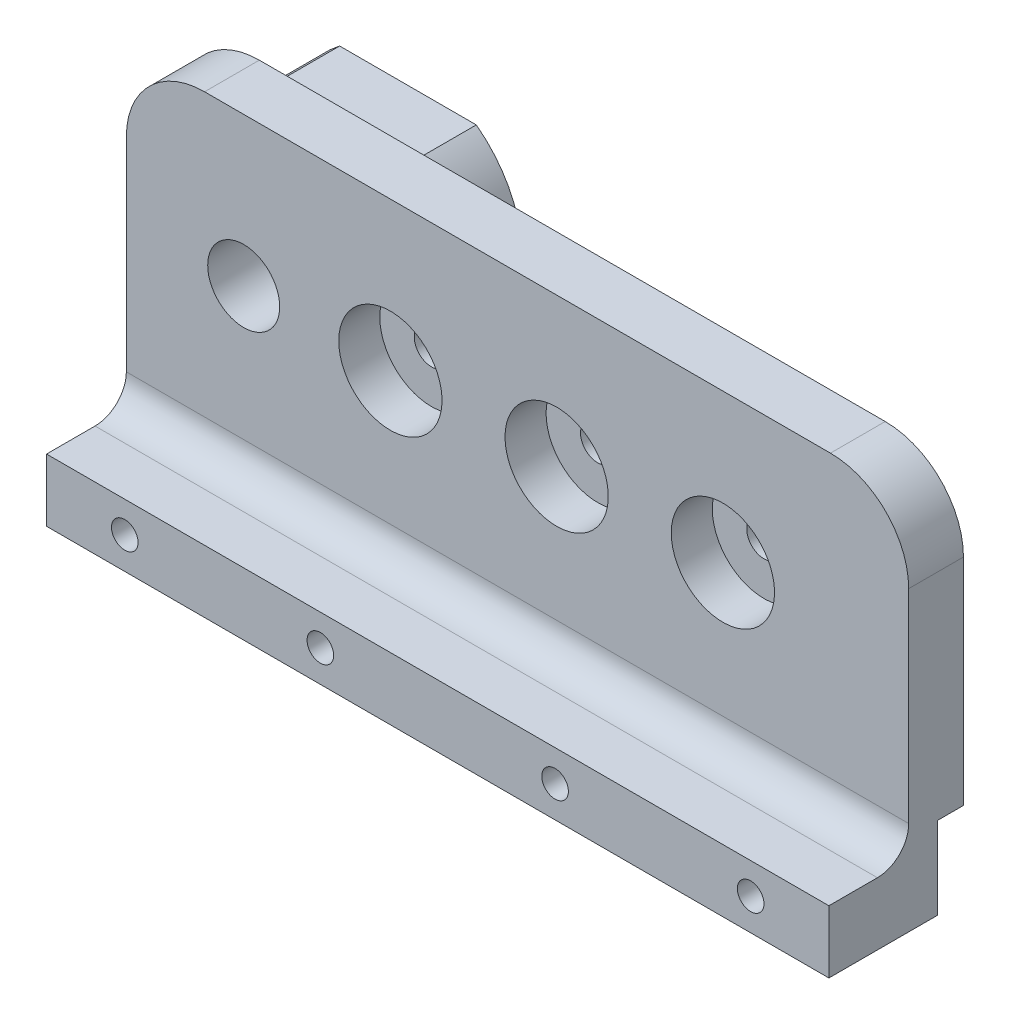
SolidWorks part; units mm, degrees
ref_plane "Front Plane" through (0, 0, 0) normal (0, 0, 1) x (1, 0, 0)
ref_plane "Top Plane" through (0, 0, 0) normal (0, 1, 0) x (1, 0, 0)
ref_plane "Right Plane" through (0, 0, 0) normal (1, 0, 0) x (0, 0, -1)
sketch "Sketch1" plane through (0, 0, 0) normal (0, 0, 1) x (1, 0, 0)
  line L1 (0, 0) -> (100, 0)
  line L2 (0, 0) -> (0, 48)
  line L3 (0, 48) -> (100, 48)
  line L4 (100, 0) -> (100, 48)
  dimension "D1" = 100
  dimension "D2" = 48
extrude "Boss-Extrude1" add sketch "Sketch1" along normal blind 7
sketch "Sketch2" plane through (0, 0, 7) normal (0, 0, 1) x (1, 0, 0)
  line L0 (0, 0) -> (100, 0) construction
  line L1 (0, 48) -> (0, 0) construction
  circle A0 centre (15, 29) radius 4.6
  circle A1 centre (33.75, 29) radius 2.2
  circle A2 centre (55, 29) radius 2.2
  circle A3 centre (76.25, 29) radius 2.2
  dimension "D1" = 4.4
  dimension "D2" = 18.75
  dimension "D3" = 21.25
  dimension "D4" = 21.25
  dimension "D5" = 29
  dimension "D6" = 15
  dimension "D7" = 9.2
extrude "Cut-Extrude1" cut sketch "Sketch2" against normal up to next
sketch "Sketch3" plane through (0, 0, 0) normal (0, 0, -1) x (-1, 0, 0)
  line L0 (0, 48) -> (0, 0) construction
  line L1 (-100, 0) -> (0, 0)
  line L2 (-100, 0) -> (-100, 8)
  line L3 (-100, 8) -> (0, 8)
  line L4 (0, 0) -> (0, 8)
  dimension "D1" = 8
extrude "Boss-Extrude2" add sketch "Sketch3" along normal blind 10.2
sketch "Sketch4" plane through (0, 0, 0) normal (0, 0, -1) x (-1, 0, 0)
  circle A0 centre (-76.25, 29) radius 6.6
  circle A1 centre (-55, 29) radius 6.6
  circle A2 centre (-33.75, 29) radius 6.6
  dimension "D1" = 13.2
extrude "Cut-Extrude2" cut sketch "Sketch4" against normal blind 5.25
sketch "Sketch5" plane through (0, 0, 7) normal (0, 0, 1) x (1, 0, 0)
  line L0 (35, 4.0521) -> (65, 4) construction
  line L1 (0, 0) -> (100, 0) construction
  circle A0 centre (35, 4.0521) radius 2.6
  circle A1 centre (65, 4) radius 2.6
  point P6 (50, 0)
  point P7 (50, 4.0261)
  dimension "D1" = 5.2
  dimension "D2" = 30
  dimension "D3" = 4
extrude "Cut-Extrude3" cut sketch "Sketch5" against normal blind 0.1
sketch "Sketch7" plane through (0, 0, 6.9) normal (0, 0, 1) x (1, 0, 0)
  circle A0 centre (35, 4.0521) radius 1.7
  circle A1 centre (65, 4) radius 1.7
  dimension "D1" = 3.4
extrude "Cut-Extrude4" cut sketch "Sketch7" against normal through all
sketch "Sketch8" plane through (0, 0, 7) normal (0, 0, 1) x (1, 0, 0)
  line L0 (10, 4.0521) -> (35, 4.0521) construction
  line L1 (0, 48) -> (0, 0) construction
  line L2 (100, 0) -> (100, 48) construction
  circle A0 centre (10, 4.0521) radius 1.7
  circle A1 centre (90, 4.0521) radius 1.7
  dimension "D1" = 3.4
  dimension "D2" = 10
  dimension "D3" = 10
extrude "Cut-Extrude5" cut sketch "Sketch8" against normal up to next
mirror "Mirror1" about plane through (0, 0, -10.2) normal (0, 0, 1) of bodies 110
delete or keep bodies "Body-Delete/Keep 1" type delete bodies bodies 110
sketch "Sketch9" plane through (100, 0, 0) normal (1, 0, 0) x (0, 0, -1)
  line L1 (27.4, 0) -> (24.1, 0)
  line L2 (27.4, 0) -> (27.4, 10.5)
  line L3 (27.4, 10.5) -> (24.1, 10.5)
  line L4 (24.1, 0) -> (24.1, 10.5)
  dimension "D1" = 10.5
  dimension "D2" = 3.3
extrude "Cut-Extrude6" cut sketch "Sketch9" against normal up to next
sketch "Sketch10" plane through (0, 0, -27.4) normal (0, 0, -1) x (-1, 0, 0)
  line L1 (-22.8594, 38.2) -> (-7.1406, 38.2)
  line L2 (-22.8594, 38.2) -> (-22.8594, 19.8) construction
  line L3 (-22.8594, 19.8) -> (-7.1406, 19.8)
  line L4 (-7.1406, 38.2) -> (-7.1406, 19.8) construction
  line L5 (-22.8594, 38.2) -> (-7.1406, 19.8) construction
  line L6 (-22.8594, 19.8) -> (-7.1406, 38.2) construction
  circle A0 centre (-15, 29) radius 12.1
  circle M6 centre (-15, 29) radius 4.6
  dimension "D2" = 24.2
  dimension "D1" = 18.4
extrude "Boss-Extrude3" add sketch "Sketch10" along normal blind 14 separate body contours L1 A0 L3 M6 | M6 region at (15, 37.896, -27.4) region at (15, 29, -27.4)
shell "Shell1" thickness 2.5 removed face at (15, 29, -27.4) removed face at (15, 29, -41.4) outward yes
combine bodies "Combine1" operation type add bodies to combine 115 116
fillet "Fillet3" radius 10 2 edges at (0, 48, -23.9) (100, 48, -23.9)
sketch "Sketch11" plane through (0, 0, -24.1) normal (0, 0, -1) x (-1, 0, 0)
  line L0 (-60.9585, 4) -> (-60.9585, 0)
  line L1 (-62.9793, 0.5) -> (-60.9585, 4) construction
  line L2 (-60.9585, 4) -> (-62.9793, 7.5)
  line L3 (-62.9793, 7.5) -> (-67.0207, 7.5)
  line L4 (-67.0207, 7.5) -> (-69.0414, 4)
  line L5 (-69.0414, 4) -> (-67.0207, 0.5) construction
  line L6 (-67.0207, 0.5) -> (-62.9793, 0.5) construction
  line L7 (0, 0) -> (-100, 0) construction
  line L8 (-69.0414, 4) -> (-69.0414, 0)
  line L9 (-60.9585, 0) -> (-69.0414, 0)
  line L10 (-38.9813, 4.0521) -> (-38.9813, 0)
  line L11 (-33.0094, 0.6043) -> (-31.0188, 4.0521) construction
  line L12 (-31.0188, 4.0521) -> (-33.0094, 7.5)
  line L13 (-33.0094, 7.5) -> (-36.9906, 7.5)
  line L14 (-36.9906, 7.5) -> (-38.9813, 4.0521)
  line L15 (-38.9813, 4.0521) -> (-36.9906, 0.6043) construction
  line L16 (-36.9906, 0.6043) -> (-33.0094, 0.6043) construction
  line L17 (-38.9813, 0) -> (-31.0188, 0)
  line L18 (-31.0188, 0) -> (-31.0188, 4.0521)
  circle A0 centre (-65, 4) radius 3.5 construction
  circle A1 centre (-35, 4.0521) radius 3.4479 construction
  dimension "D1" = 7
extrude "Cut-Extrude7" cut sketch "Sketch11" against normal blind 3.2 from offset 3 offset against normal yes
sketch "Sketch12" plane through (0, 0, -24.1) normal (0, 0, -1) x (-1, 0, 0)
  line L1 (-87.9793, 0.5521) -> (-85.9585, 4.0521)
  line L2 (-85.9585, 4.0521) -> (-87.9793, 7.5521)
  line L3 (-87.9793, 7.5521) -> (-92.0207, 7.5521)
  line L4 (-92.0207, 7.5521) -> (-94.0415, 4.0521)
  line L5 (-94.0415, 4.0521) -> (-92.0207, 0.5521)
  line L6 (-92.0207, 0.5521) -> (-87.9793, 0.5521)
  line L7 (-7.9793, 0.5521) -> (-5.9585, 4.0521)
  line L8 (-5.9585, 4.0521) -> (-7.9793, 7.5521)
  line L9 (-7.9793, 7.5521) -> (-12.0207, 7.5521)
  line L10 (-12.0207, 7.5521) -> (-14.0415, 4.0521)
  line L11 (-14.0415, 4.0521) -> (-12.0207, 0.5521)
  line L12 (-12.0207, 0.5521) -> (-7.9793, 0.5521)
  circle A0 centre (-90, 4.0521) radius 3.5 construction
  circle A1 centre (-10, 4.0521) radius 3.5 construction
  circle A2 centre (-10, 4.0521) radius 1.7 construction
  point P20 (0, 0)
  dimension "D1" = 7
extrude "Cut-Extrude8" cut sketch "Sketch12" against normal blind 5
fillet "Fillet4" radius 4 1 edges at (50, 8, -20.4)
